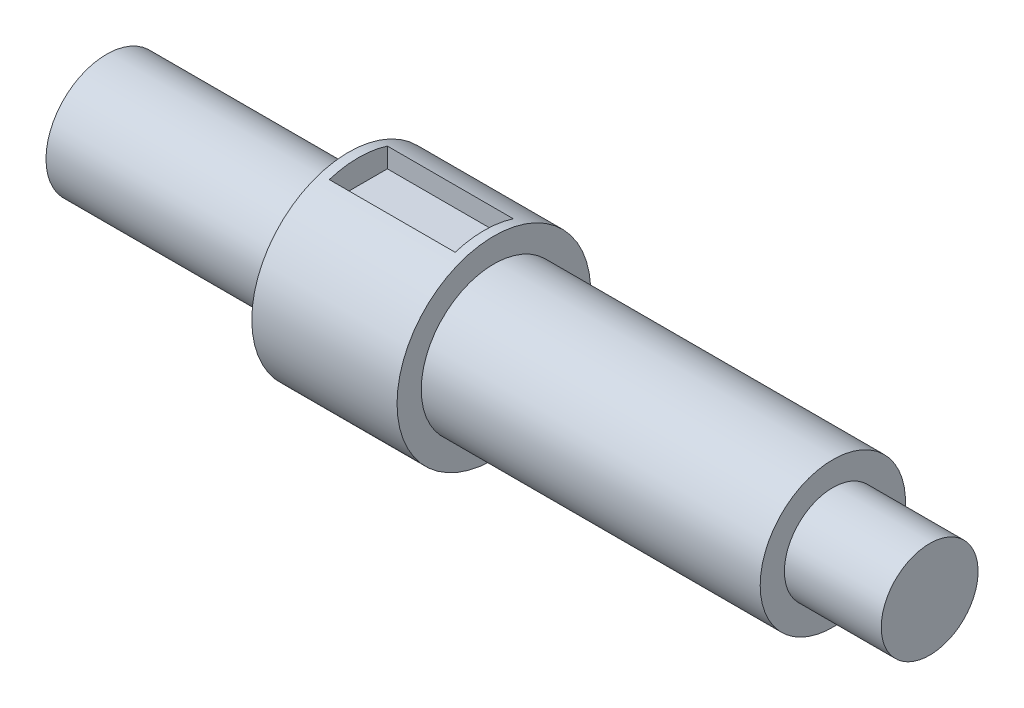
SolidWorks part; units mm, degrees
ref_plane "前视基准面" through (0, 0, 0) normal (0, 0, 1) x (1, 0, 0)
ref_plane "上视基准面" through (0, 0, 0) normal (0, 1, 0) x (1, 0, 0)
ref_plane "右视基准面" through (0, 0, 0) normal (1, 0, 0) x (0, 0, -1)
other "Configuration Table"
sketch "草图1" plane through (0, 0, 0) normal (0, 0, 1) x (1, 0, 0)
  line L0 (-10, 0) -> (180, 0) construction
  line L1 (0, 0) -> (170, 0)
  line L2 (170, 0) -> (170, 10)
  line L3 (170, 10) -> (150, 10)
  line L4 (150, 10) -> (150, 15)
  line L5 (150, 15) -> (80, 15)
  line L6 (80, 15) -> (80, 20)
  line L7 (80, 20) -> (50, 20)
  line L8 (50, 20) -> (50, 12.5)
  line L9 (50, 12.5) -> (0, 12.5)
  line L10 (0, 12.5) -> (0, 0)
revolve "旋转1" add sketch "草图1" angle 360 about L0
sketch "草图2" plane through (0, 0, 0) normal (0, 0, 1) x (1, 0, 0)
  line L1 (52, 15) -> (78, 15)
  line L2 (52, 15) -> (52, 25)
  line L3 (52, 25) -> (78, 25)
  line L4 (78, 15) -> (78, 25)
extrude "切除-拉伸1" cut sketch "草图2" along normal blind 6 and the other way blind 6
